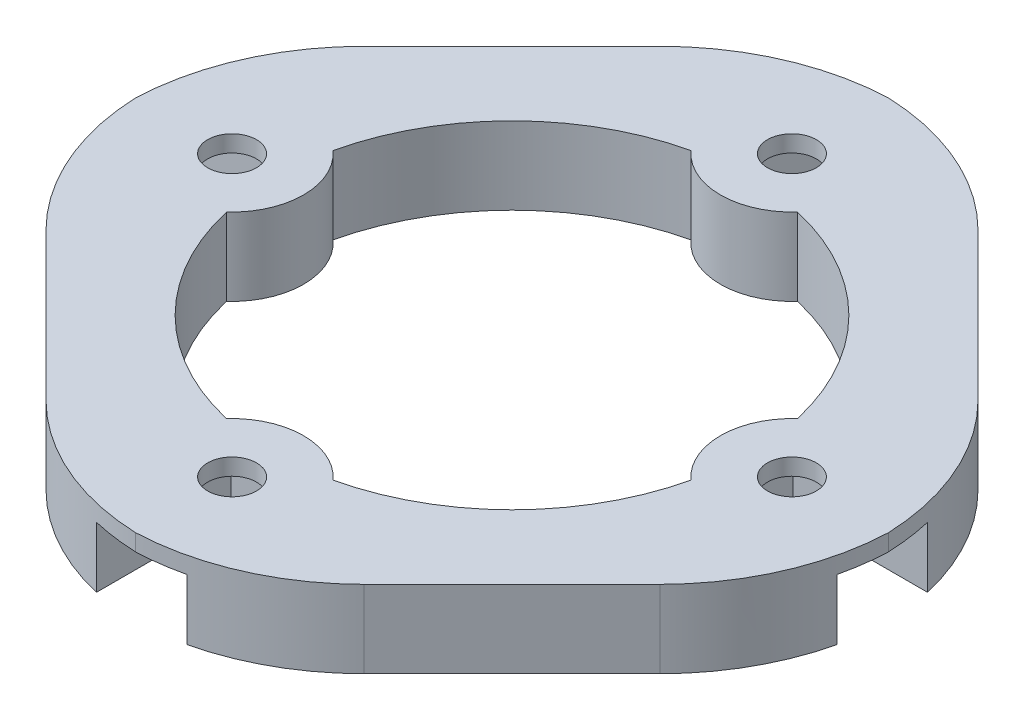
SolidWorks part; units mm, degrees
ref_plane "Спереди" through (0, 0, 0) normal (0, 0, 1) x (1, 0, 0)
ref_plane "Сверху" through (0, 0, 0) normal (0, 1, 0) x (1, 0, 0)
ref_plane "Справа" through (0, 0, 0) normal (1, 0, 0) x (0, 0, -1)
sketch "Sketch1" plane through (0, 0, 0) normal (0, 1, 0) x (1, 0, 0)
  circle A0 centre (0, 0) radius 65
  circle A1 centre (0, 0) radius 40
  dimension "D1" = 130
  dimension "D2" = 80
extrude "Boss-Extrude1" add sketch "Sketch1" along normal blind 13
sketch "Sketch2" plane through (0, 13, 0) normal (0, 1, 0) x (1, 0, 0)
  line L0 (0, 65) -> (0, -65) construction
  line L1 (-65, 0) -> (65, 0) construction
  circle A0 centre (0, 0) radius 65 construction
  circle A1 centre (0, 47) radius 4.1
  circle A2 centre (47, 0) radius 4.1
  circle A3 centre (0, -47) radius 4.1
  circle A4 centre (-47, 0) radius 4.1
  circle A5 centre (0, 0) radius 47 construction
  dimension "D1" = 8.2
extrude "Cut-Extrude1" cut sketch "Sketch2" against normal through all
sketch "Sketch8" plane through (0, 13, 0) normal (0, 1, 0) x (1, 0, 0)
  circle A0 centre (47, 0) radius 12
  circle A1 centre (0, -47) radius 12
  circle A2 centre (-47, 0) radius 12
  circle A3 centre (0, 47) radius 12
  circle A4 centre (0, 47) radius 4.1
  circle A5 centre (47, 0) radius 4.1
  circle A6 centre (0, -47) radius 4.1
  circle A7 centre (-47, 0) radius 4.1
  circle A8 centre (-47, 0) radius 4.1 construction
  dimension "D1" = 24
extrude "Boss-Extrude4" add sketch "Sketch8" against normal up to surface (13 mm away) up to face at (47, 0, 4.1)
sketch "Sketch3" plane through (0, 0, 0) normal (0, -1, 0) x (1, 0, 0)
  line L0 (-35.7148, 0) -> (-65, 0) construction
  line L1 (7.6, 39.6) -> (-7.6, 39.6)
  line L2 (7.6, 39.6) -> (7.6, 79.6)
  line L3 (7.6, 79.6) -> (-7.6, 79.6)
  line L4 (-7.6, 39.6) -> (-7.6, 79.6)
  line L5 (7.6, 39.6) -> (-7.6, 79.6) construction
  line L6 (7.6, 79.6) -> (-7.6, 39.6) construction
  line L7 (79.6, -7.6) -> (39.6, -7.6)
  line L8 (79.6, -7.6) -> (79.6, 7.6)
  line L9 (79.6, 7.6) -> (39.6, 7.6)
  line L10 (39.6, -7.6) -> (39.6, 7.6)
  line L11 (79.6, -7.6) -> (39.6, 7.6) construction
  line L12 (79.6, 7.6) -> (39.6, -7.6) construction
  line L13 (7.6, -79.6) -> (-7.6, -79.6)
  line L14 (7.6, -79.6) -> (7.6, -39.6)
  line L15 (7.6, -39.6) -> (-7.6, -39.6)
  line L16 (-7.6, -79.6) -> (-7.6, -39.6)
  line L17 (7.6, -79.6) -> (-7.6, -39.6) construction
  line L18 (7.6, -39.6) -> (-7.6, -79.6) construction
  line L19 (-39.6, -7.6) -> (-79.6, -7.6)
  line L20 (-39.6, -7.6) -> (-39.6, 7.6)
  line L21 (-39.6, 7.6) -> (-79.6, 7.6)
  line L22 (-79.6, -7.6) -> (-79.6, 7.6)
  line L23 (-39.6, -7.6) -> (-79.6, 7.6) construction
  line L24 (-39.6, 7.6) -> (-79.6, -7.6) construction
  line L25 (0, -35) -> (0, -65) construction
  line L26 (35, 0) -> (65, 0) construction
  line L27 (0, 35) -> (0, 47) construction
  line L28 (0, 47) -> (0, 65) construction
  circle A0 centre (0, 0) radius 65 construction
  arc A1 (8.9347, -38.9894) -> (-8.9347, -38.9894) centre (0, -47) ccw construction
  arc A2 (38.9894, 8.9347) -> (38.9894, -8.9347) centre (47, 0) ccw construction
  arc A3 (-8.9347, 38.9894) -> (8.9347, 38.9894) centre (0, 47) ccw construction
  circle A4 centre (0, 0) radius 59.6 construction
  point P0 (0, 59.6)
  point P6 (59.6, 0)
  point P12 (0, -59.6)
  point P17 (0, 0)
  point P18 (-59.6, 0)
  point P23 (0, 0)
  point P46 (0, 0)
  point P48 (0, 0)
  dimension "D1" = 15.2
  dimension "D2" = 7.4
  dimension "D3" = 40
extrude "Cut-Extrude2" cut sketch "Sketch3" against normal blind 10.2
sketch "Sketch4" plane through (0, 13, 0) normal (0, 1, 0) x (1, 0, 0)
  line L0 (0, 0) -> (-45.9619, -45.9619) construction
  line L1 (0, 0) -> (0, -65) construction
  line L2 (-33.5876, -58.3363) -> (-58.3363, -33.5876)
  line L3 (-58.3363, -33.5876) -> (-56.6392, -31.8905)
  line L4 (-56.6392, -31.8905) -> (-31.8905, -56.6392)
  line L5 (-31.8905, -56.6392) -> (-33.5876, -58.3363)
  circle A0 centre (0, 0) radius 65 construction
  point P10 (-45.9619, -45.9619)
  dimension "D1" = 45
  dimension "D2" = 35
extrude "Boss-Extrude2" add sketch "Sketch4" against normal up to surface (13 mm away) up to face at (0, 0, 0)
fillet "Fillet1" radius 30 2 edges at (-56.6392, 6.5, 31.8905) (-31.8905, 6.5, 56.6392)
sketch "Sketch5" plane through (0, 13, 0) normal (0, 1, 0) x (1, 0, 0)
  line L0 (-45.9619, -45.9619) -> (0, 0) construction
  line L1 (-58.3363, -33.5876) -> (-33.5876, -58.3363) construction
  line L2 (0, 0) -> (-45.9619, 45.9619) construction
  line L3 (-59.2131, 31.5228) -> (-31.5228, 59.2131) construction
  line L4 (-31.5228, 59.2131) -> (-29.9819, 57.6722)
  line L5 (-59.2131, 31.5228) -> (-57.6722, 29.9819)
  line L6 (-31.5228, 59.2131) -> (-39.146, 51.5899)
  line L7 (-52.7332, 38.0027) -> (-59.2131, 31.5228)
  arc A0 (-23.9759, -60.4165) -> (-60.4165, -23.9759) centre (0, 0) ccw construction
  arc A1 (-29.9819, 57.6722) -> (-39.146, 51.5899) centre (1.2517, 0.6682) ccw
  arc A2 (-57.6722, 29.9819) -> (-52.7332, 38.0027) centre (0, 0) cw
  point P12 (-45.368, 45.368)
  dimension "D1" = 39.16
  dimension "D2" = 64.16
extrude "Boss-Extrude3" add sketch "Sketch5" against normal up to surface (13 mm away) up to face at (-8.3309, 0, 8.3309)
sketch "Sketch6" plane through (0, 13, 0) normal (0, 1, 0) x (1, 0, 0)
  line L0 (-31.5228, 59.2131) -> (-59.2131, 31.5228)
  line L1 (-59.2131, 31.5228) -> (-61.4944, 33.8041)
  line L2 (-61.4944, 33.8041) -> (-33.8041, 61.4944)
  line L3 (-33.8041, 61.4944) -> (-31.5228, 59.2131)
extrude "Cut-Extrude3" cut sketch "Sketch6" against normal through all
fillet "Fillet2" radius 30 2 edges at (-57.6722, 6.5, -29.9819) (-29.9819, 6.5, -57.6722)
sketch "Sketch7" plane through (0, 13, 0) normal (0, 1, 0) x (1, 0, 0)
  line L0 (63.2456, -15) -> (15, -63.2456)
  line L1 (15, -63.2456) -> (-15, -63.2456)
  line L2 (-15, -63.2456) -> (-63.2456, -15)
  line L3 (-63.2456, -15) -> (-63.2456, 15)
  line L4 (-63.2456, 15) -> (-15, 63.2456)
  line L5 (-15, 63.2456) -> (15, 63.2456)
  line L6 (15, 63.2456) -> (63.2456, 15)
  line L7 (63.2456, 15) -> (63.2456, -15)
  line L8 (47, 0) -> (0, 0) construction
  line L9 (47, 0) -> (63.2456, 0) construction
  arc A0 (-23.9759, -60.4165) -> (-22.3837, 61.0244) centre (0, 0) ccw construction
  arc A1 (-61.0244, 22.3837) -> (-60.4165, -23.9759) centre (0, 0) ccw construction
  point P18 (63.6273, 0)
  dimension "D1" = 30
extrude "Cut-Extrude4" cut sketch "Sketch7" against normal through all flip side to cut
fillet "Fillet3" radius 40 8 edges at (15, 6.5, 63.2456) (-15, 6.5, 63.2456) (-63.2456, 6.5, 15) (-63.2456, 6.5, -15) (-15, 6.5, -63.2456) (15, 6.5, -63.2456) (63.2456, 6.5, 15) (63.2456, 6.5, -15)
